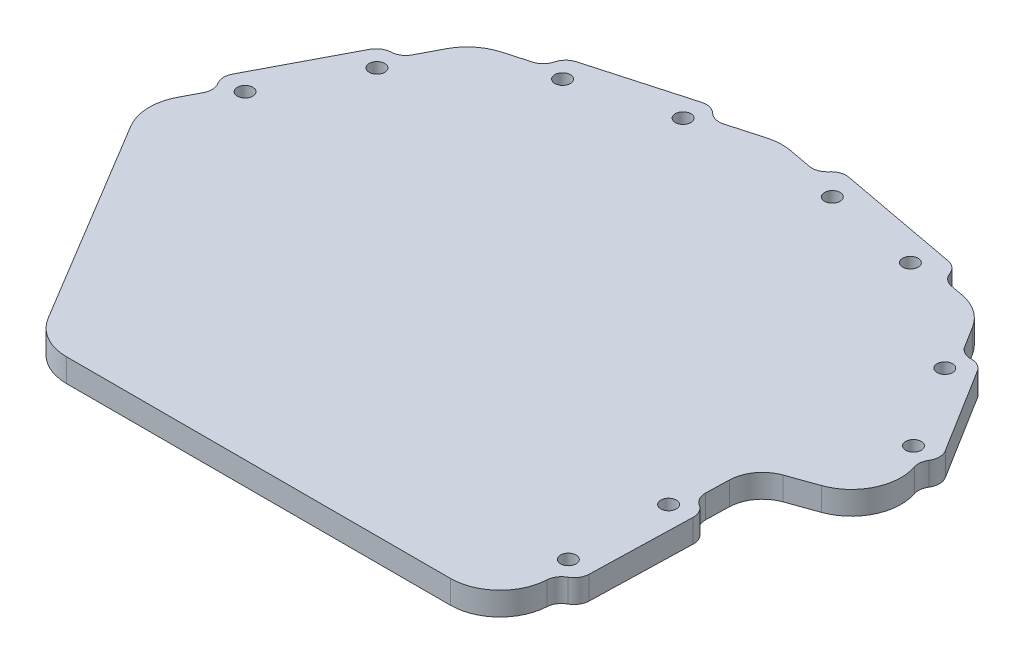
SolidWorks part; units mm, degrees
ref_plane "Front Plane" through (0, 0, 0) normal (0, 0, 1) x (1, 0, 0)
ref_plane "Top Plane" through (0, 0, 0) normal (0, 1, 0) x (1, 0, 0)
ref_plane "Right Plane" through (0, 0, 0) normal (1, 0, 0) x (0, 0, -1)
sketch "Sketch1" plane through (0, 0, 0) normal (0, 1, 0) x (1, 0, 0)
  line L0 (-45.7795, -24.4094) -> (29.5961, -24.4094)
  line L1 (-45.7795, -24.4094) -> (-70.9967, 17.4818)
  line L2 (-70.9967, 17.4818) -> (-52.1539, 53.4895)
  line L3 (-52.1539, 53.4895) -> (-13.0312, 64.4906)
  line L4 (-13.0312, 64.4906) -> (26.9178, 57.0283)
  line L5 (26.9178, 57.0283) -> (48.3987, 22.5294)
  line L6 (48.3987, 22.5294) -> (30.6718, 16.2164)
  line L7 (30.6718, 16.2164) -> (29.5961, -24.4094)
  line L9 (-61.5753, 35.4857) -> (-60.4501, 34.8968) construction
  line L10 (-61.5753, 35.4857) -> (-63.8258, 36.6633) construction
  line L11 (-69.8714, 16.8929) -> (-51.2827, 52.4153) construction
  line L12 (-51.2827, 52.4153) -> (-12.9729, 63.1878) construction
  line L13 (-12.9729, 63.1878) -> (26.1351, 55.8826) construction
  line L14 (26.1351, 55.8826) -> (47.3206, 21.8581) construction
  line L15 (-32.5926, 58.9901) -> (-32.2488, 57.7675) construction
  line L16 (6.9433, 60.7595) -> (6.7101, 59.5111) construction
  line L17 (-66.286, 26.4837) -> (-68.5365, 27.6614)
  line L18 (29.0762, 3.9381) -> (28.6525, -12.0639) construction
  line L19 (30.1339, -4.0965) -> (28.8644, -4.0629) construction
  line L20 (-68.5365, 27.6614) -> (-59.1151, 45.6653)
  line L21 (-59.1151, 45.6653) -> (-56.8646, 44.4876)
  line L22 (-67.4112, 27.0725) -> (-57.9899, 45.0764) construction
  line L23 (-42.3733, 56.2398) -> (-43.0608, 58.685)
  line L24 (-43.0608, 58.685) -> (-23.4995, 64.1855)
  line L25 (-23.4995, 64.1855) -> (-22.8119, 61.7403)
  line L26 (-32.5926, 58.9901) -> (-33.2802, 61.4352) construction
  line L27 (-42.7171, 57.4624) -> (-23.1557, 62.9629) construction
  line L28 (-4.8782, 62.9677) -> (-4.4118, 65.4645)
  line L29 (-4.4118, 65.4645) -> (19.2312, 61.0481)
  line L30 (19.2312, 61.0481) -> (18.7648, 58.5513)
  line L31 (-4.645, 64.2161) -> (18.998, 59.7997) construction
  line L32 (6.9433, 60.7595) -> (7.1765, 62.0079) construction
  line L33 (37.6583, 39.7788) -> (39.8144, 41.1214) construction
  line L34 (32.288, 48.4036) -> (34.4442, 49.7461)
  line L35 (34.4442, 49.7461) -> (45.1847, 32.4967)
  line L36 (45.1847, 32.4967) -> (43.0285, 31.1541)
  line L37 (33.3661, 49.0749) -> (44.1066, 31.8254) construction
  line L38 (30.4028, 6.0599) -> (32.9428, 5.9927)
  line L39 (32.9428, 5.9927) -> (32.405, -14.3202)
  line L40 (32.405, -14.3202) -> (29.865, -14.2529)
  line L41 (30.1339, -4.0965) -> (32.6739, -4.1638) construction
  line L42 (31.6728, 6.0263) -> (31.135, -14.2866) construction
  circle A0 centre (-64.1597, 27.8078) radius 1.27
  circle A1 centre (-56.7404, 41.9859) radius 1.27
  circle A2 centre (-39.9511, 55.6017) radius 1.27
  circle A3 centre (-24.5465, 59.9333) radius 1.27
  circle A4 centre (-1.1549, 60.9802) radius 1.27
  circle A5 centre (14.575, 58.0419) radius 1.27
  circle A6 centre (32.3511, 45.8995) radius 1.27
  circle A7 centre (40.8092, 32.3156) radius 1.27
  circle A8 centre (29.0762, 3.9381) radius 1.27
  circle A9 centre (28.6525, -12.0639) radius 1.27
  point P84 (39.8144, 41.1214)
  point P94 (32.6739, -4.1638)
  dimension "D8" = 16.002
  dimension "D11" = 16.002
  dimension "D12" = 8.001
  dimension "D7" = 2.54
  dimension "D9" = 16.002
  dimension "D10" = 16.002
  dimension "D15" = 20.32
  dimension "D16" = 2.54
  dimension "D1" = 40.64
  dimension "D2" = 40.64
  dimension "D3" = 40.64
  dimension "D4" = 40.64
  dimension "D5" = 40.64
  dimension "D6" = 1.27
  dimension "D13" = 8.001
  dimension "D14" = 8.001
  dimension "D17" = 1.27
  dimension "D18" = 16.002
  dimension "D19" = 88.9
  dimension "D20" = 8.001
  dimension "D28" = 2.54
extrude "Boss-Extrude1" add sketch "Sketch1" along normal blind 3.81 contours L7 L6 L5 L4 L3 L2 L1 L0 | L21 L20 L17 L2 | L25 L24 L23 L3 | L30 L29 L28 L4 | L36 L35 L34 L5 | L40 L39 L38 L7 region at (-12.62, 0, -18.376) region at (31.4039, 0, 4.1301) region at (-62.7006, 0, -36.0745) region at (-32.9364, 0, -60.2127) region at (38.7363, 0, -40.4501) region at (7.1765, 0, -62.0079)
fillet "Fillet1" radius 8.128 7 edges at (-70.9967, 1.905, -17.4818) (-52.1539, 1.905, -53.4895) (-13.0312, 1.905, -64.4906) (26.9178, 1.905, -57.0283) (48.3987, 1.905, -22.5294) (-45.7795, 1.905, 24.4094) (29.5961, 1.905, 24.4094)
fillet "Fillet2" radius 5.588 1 edges at (30.6718, 1.905, -16.2164)
fillet "Fillet3" radius 2.54 10 edges at (43.0285, 1.905, -31.1541) (29.865, 1.905, 14.2529) (30.4028, 1.905, -6.0599) (-66.286, 1.905, -26.4837) (-56.8646, 1.905, -44.4876) (-42.3733, 1.905, -56.2398) (-22.8119, 1.905, -61.7403) (-4.8782, 1.905, -62.9677) (18.7648, 1.905, -58.5513) (32.288, 1.905, -48.4036)
fillet "Fillet4" radius 2.54 10 edges at (32.405, 1.905, 14.3202) (32.9428, 1.905, -5.9927) (45.1847, 1.905, -32.4967) (34.4442, 1.905, -49.7461) (19.2312, 1.905, -61.0481) (-4.4118, 1.905, -65.4645) (-23.4995, 1.905, -64.1855) (-43.0608, 1.905, -58.685) (-59.1151, 1.905, -45.6653) (-68.5365, 1.905, -27.6614)
